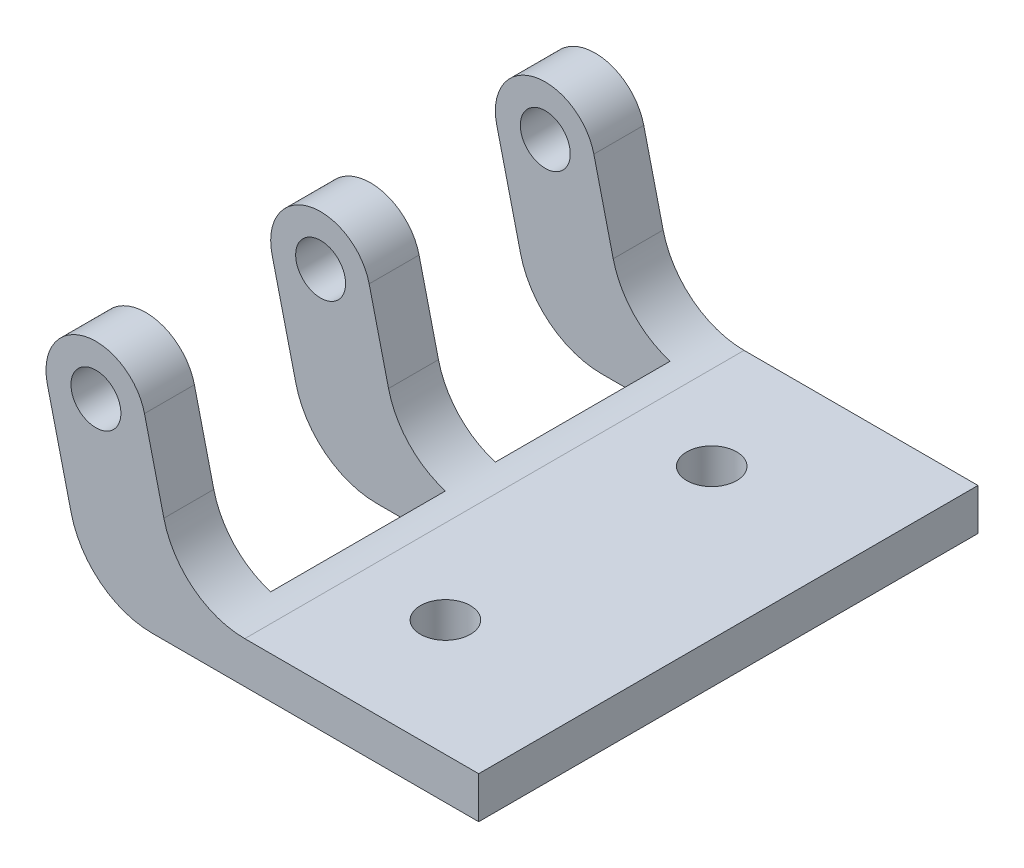
SolidWorks part; units mm, degrees
ref_plane "Plano frontal" through (0, 0, 0) normal (0, 0, 1) x (1, 0, 0)
ref_plane "Plano superior" through (0, 0, 0) normal (0, 1, 0) x (1, 0, 0)
ref_plane "Plano direito" through (0, 0, 0) normal (1, 0, 0) x (0, 0, -1)
sketch "Esboço1" plane through (0, 0, 0) normal (0, 0, 1) x (1, 0, 0)
  line L0 (-9, 0) -> (9, 0)
  line L1 (9, 0) -> (9, -2.5)
  line L2 (9, -2.5) -> (-14.571, -2.5)
  line L3 (-14.571, -2.5) -> (-16.9176, 7.3015)
  line L4 (-9, 0) -> (-11.0824, 8.6985)
  line L5 (10, -5.8654) -> (10, 13.9047) construction
  line L6 (-35, 68.0735) -> (7, 68.0735) construction
  line L7 (-35, 68.0735) -> (-35, 26.0735) construction
  line L8 (-35, 26.0735) -> (7, 26.0735) construction
  line L9 (7, 68.0735) -> (7, 26.0735) construction
  line L10 (-35, 68.0735) -> (7, 26.0735) construction
  line L11 (-35, 26.0735) -> (7, 68.0735) construction
  line L12 (-7.5, 47.0735) -> (-7.5, 8) construction
  circle A0 centre (-14, 8) radius 1.5
  arc A1 (-11.0824, 8.6985) -> (-16.9176, 7.3015) centre (-14, 8) ccw
  circle A2 centre (-14, 8) radius 6.5 construction
  circle A3 centre (-14, 47.0735) radius 6.5 construction
  point P7 (0, 0)
  point P11 (-14, 47.0735)
  point P22 (-14, 47.0735)
  dimension "D1" = 3
  dimension "D5" = 6
  dimension "D9" = 13
  dimension "D10" = 13
  dimension "D2" = 2.5
  dimension "D3" = 18
  dimension "D4" = 8
  dimension "D6" = 42
  dimension "D7" = 10
  dimension "D8" = 3
extrude "Ressalto-extrusão1" add sketch "Esboço1" along normal blind 30
fillet "Filete1" radius 5 2 edges at (-14.571, -2.5, 15) (-9, 0, 15)
sketch "Esboço2" plane through (0, 0, 0) normal (0, 1, 0) x (1, 0, 0)
  line L0 (-17, 0) -> (-17, -30) construction
  line L1 (-17, -3) -> (-6.5, -3)
  line L2 (-17, -3) -> (-17, -13.5)
  line L3 (-17, -13.5) -> (-6.5, -13.5)
  line L4 (-6.5, -3) -> (-6.5, -13.5)
  line L7 (-17, -16.5) -> (-6.5, -16.5)
  line L8 (-17, -16.5) -> (-17, -27)
  line L9 (-17, -27) -> (-6.5, -27)
  line L10 (-6.5, -16.5) -> (-6.5, -27)
  line L12 (9, -15) -> (-18.9332, -15) construction
  line L13 (9, -30) -> (9, 0) construction
  circle A0 centre (0, -7) radius 1.5
  circle A1 centre (0, -23) radius 1.5
  point P16 (-17, -16)
  point P17 (0, -22.5664)
  point P23 (0, 0)
  point P25 (0, 0)
  point P27 (0, -23.1654)
  dimension "D4" = 3
  dimension "D1" = 10.5
  dimension "D2" = 10.5
  dimension "D3" = 3
  dimension "D5" = 16
  dimension "D6" = 10.5
extrude "Corte-extrusão1" cut sketch "Esboço2" against normal through all both and the other way through all
